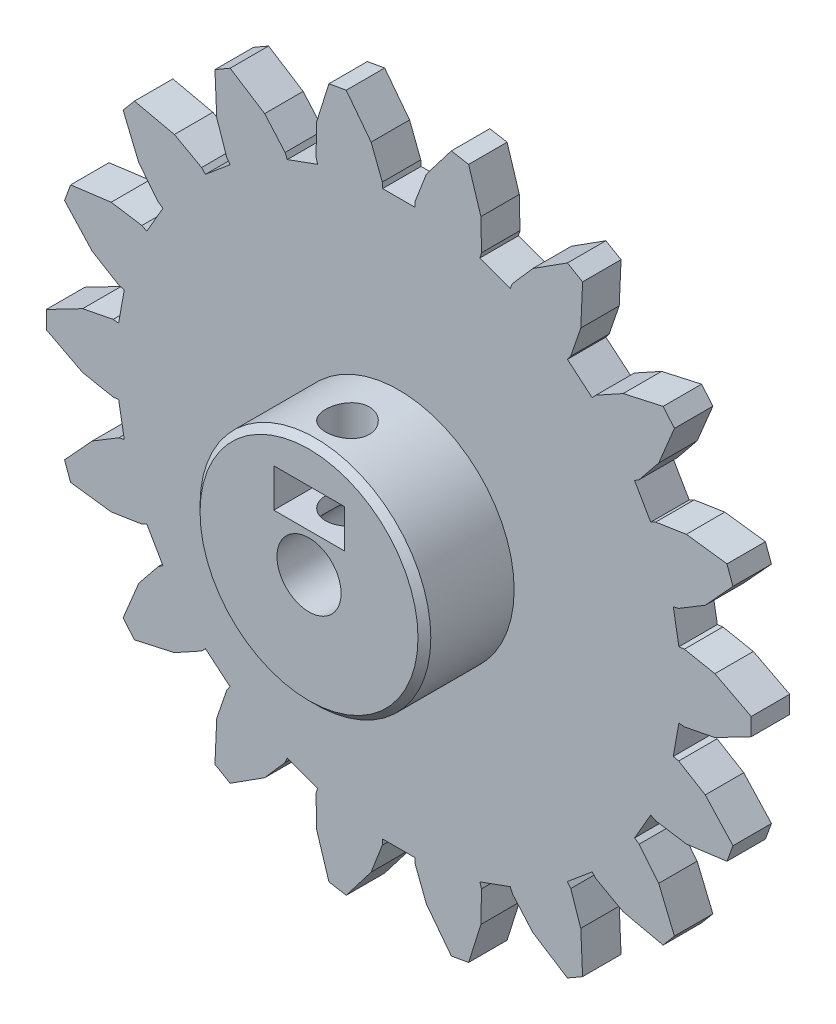
SolidWorks part; units mm, degrees
material "ABS"
ref_plane "Front Plane" through (0, 0, 0) normal (0, 0, 1) x (1, 0, 0)
ref_plane "Top Plane" through (0, 0, 0) normal (0, 1, 0) x (1, 0, 0)
ref_plane "Right Plane" through (0, 0, 0) normal (1, 0, 0) x (0, 0, -1)
sketch "Sketch1" plane through (0, 0, 0) normal (0, 0, 1) x (1, 0, 0)
  line L0 (52.5388, 31.8426) -> (52.9668, 31.8929)
  line L1 (52.9668, 31.8929) -> (55.3456, 31.4261)
  line L2 (55.3456, 31.4261) -> (58.181, 29.9538)
  line L3 (58.181, 29.9538) -> (58.181, 28.5845)
  line L4 (58.181, 28.5845) -> (55.3456, 27.1121)
  line L5 (55.3456, 27.1121) -> (52.9668, 26.6454)
  line L6 (52.9668, 26.6454) -> (52.5388, 26.6957)
  line L7 (52.5388, 26.6957) -> (52.1012, 24.2147)
  line L8 (52.1012, 24.2147) -> (52.5208, 24.1156)
  line L9 (52.5208, 24.1156) -> (54.5964, 22.8636)
  line L10 (54.5964, 22.8636) -> (56.7575, 20.51)
  line L11 (56.7575, 20.51) -> (56.2891, 19.2232)
  line L12 (56.2891, 19.2232) -> (53.1208, 18.8096)
  line L13 (53.1208, 18.8096) -> (50.726, 19.1845)
  line L14 (50.726, 19.1845) -> (50.3409, 19.3783)
  line L15 (50.3409, 19.3783) -> (49.0813, 17.1964)
  line L16 (49.0813, 17.1964) -> (49.4416, 16.9599)
  line L17 (49.4416, 16.9599) -> (50.9638, 15.0733)
  line L18 (50.9638, 15.0733) -> (52.1897, 12.1228)
  line L19 (52.1897, 12.1228) -> (51.3094, 11.0736)
  line L20 (51.3094, 11.0736) -> (48.1906, 11.7686)
  line L21 (48.1906, 11.7686) -> (46.0686, 12.9399)
  line L22 (46.0686, 12.9399) -> (45.7729, 13.2537)
  line L23 (45.7729, 13.2537) -> (43.8429, 11.6343)
  line L24 (43.8429, 11.6343) -> (44.1008, 11.2887)
  line L25 (44.1008, 11.2887) -> (44.8859, 8.9954)
  line L26 (44.8859, 8.9954) -> (45.0287, 5.8036)
  line L27 (45.0287, 5.8036) -> (43.8427, 5.1188)
  line L28 (43.8427, 5.1188) -> (41.1496, 6.8384)
  line L29 (41.1496, 6.8384) -> (39.5561, 8.665)
  line L30 (39.5561, 8.665) -> (39.3857, 9.0611)
  line L31 (39.3857, 9.0611) -> (37.0183, 8.1993)
  line L32 (37.0183, 8.1993) -> (37.1423, 7.7863)
  line L33 (37.1423, 7.7863) -> (37.0957, 5.3628)
  line L34 (37.0957, 5.3628) -> (36.1382, 2.3147)
  line L35 (36.1382, 2.3147) -> (34.7894, 2.0769)
  line L36 (34.7894, 2.0769) -> (32.8471, 4.6136)
  line L37 (32.8471, 4.6136) -> (31.9745, 6.8751)
  line L38 (31.9745, 6.8751) -> (31.9497, 7.3056)
  line L39 (31.9497, 7.3056) -> (29.4305, 7.3056)
  line L40 (29.4305, 7.3056) -> (29.4057, 6.8751)
  line L41 (29.4057, 6.8751) -> (28.5331, 4.6136)
  line L42 (28.5331, 4.6136) -> (26.5908, 2.0769)
  line L43 (26.5908, 2.0769) -> (25.242, 2.3147)
  line L44 (25.242, 2.3147) -> (24.2845, 5.3628)
  line L45 (24.2845, 5.3628) -> (24.2379, 7.7863)
  line L46 (24.2379, 7.7863) -> (24.3618, 8.1993)
  line L47 (24.3618, 8.1993) -> (21.9945, 9.0611)
  line L48 (21.9945, 9.0611) -> (21.8241, 8.665)
  line L49 (21.8241, 8.665) -> (20.2306, 6.8384)
  line L50 (20.2306, 6.8384) -> (17.5375, 5.1188)
  line L51 (17.5375, 5.1188) -> (16.3515, 5.8036)
  line L52 (16.3515, 5.8036) -> (16.4943, 8.9954)
  line L53 (16.4943, 8.9954) -> (17.2794, 11.2887)
  line L54 (17.2794, 11.2887) -> (17.5373, 11.6343)
  line L55 (17.5373, 11.6343) -> (15.6073, 13.2537)
  line L56 (15.6073, 13.2537) -> (15.3116, 12.9399)
  line L57 (15.3116, 12.9399) -> (13.1896, 11.7686)
  line L58 (13.1896, 11.7686) -> (10.0708, 11.0736)
  line L59 (10.0708, 11.0736) -> (9.1905, 12.1228)
  line L60 (9.1905, 12.1228) -> (10.4164, 15.0733)
  line L61 (10.4164, 15.0733) -> (11.9386, 16.9599)
  line L62 (11.9386, 16.9599) -> (12.2989, 17.1964)
  line L63 (12.2989, 17.1964) -> (11.0393, 19.3783)
  line L64 (11.0393, 19.3783) -> (10.6542, 19.1845)
  line L65 (10.6542, 19.1845) -> (8.2594, 18.8096)
  line L66 (8.2594, 18.8096) -> (5.0911, 19.2232)
  line L67 (5.0911, 19.2232) -> (4.6227, 20.51)
  line L68 (4.6227, 20.51) -> (6.7838, 22.8636)
  line L69 (6.7838, 22.8636) -> (8.8594, 24.1156)
  line L70 (8.8594, 24.1156) -> (9.279, 24.2147)
  line L71 (9.279, 24.2147) -> (8.8414, 26.6957)
  line L72 (8.8414, 26.6957) -> (8.4134, 26.6454)
  line L73 (8.4134, 26.6454) -> (6.0345, 27.1121)
  line L74 (6.0345, 27.1121) -> (3.1991, 28.5845)
  line L75 (3.1991, 28.5845) -> (3.1991, 29.9538)
  line L76 (3.1991, 29.9538) -> (6.0345, 31.4261)
  line L77 (6.0345, 31.4261) -> (8.4134, 31.8929)
  line L78 (8.4134, 31.8929) -> (8.8414, 31.8426)
  line L79 (8.8414, 31.8426) -> (9.279, 34.3235)
  line L80 (9.279, 34.3235) -> (8.8594, 34.4227)
  line L81 (8.8594, 34.4227) -> (6.7838, 35.6747)
  line L82 (6.7838, 35.6747) -> (4.6227, 38.0283)
  line L83 (4.6227, 38.0283) -> (5.0911, 39.3151)
  line L84 (5.0911, 39.3151) -> (8.2594, 39.7287)
  line L85 (8.2594, 39.7287) -> (10.6542, 39.3537)
  line L86 (10.6542, 39.3537) -> (11.0393, 39.16)
  line L87 (11.0393, 39.16) -> (12.2989, 41.3418)
  line L88 (12.2989, 41.3418) -> (11.9386, 41.5783)
  line L89 (11.9386, 41.5783) -> (10.4164, 43.4649)
  line L90 (10.4164, 43.4649) -> (9.1905, 46.4155)
  line L91 (9.1905, 46.4155) -> (10.0708, 47.4647)
  line L92 (10.0708, 47.4647) -> (13.1896, 46.7697)
  line L93 (13.1896, 46.7697) -> (15.3116, 45.5984)
  line L94 (15.3116, 45.5984) -> (15.6073, 45.2846)
  line L95 (15.6073, 45.2846) -> (17.5373, 46.904)
  line L96 (17.5373, 46.904) -> (17.2794, 47.2496)
  line L97 (17.2794, 47.2496) -> (16.4943, 49.5429)
  line L98 (16.4943, 49.5429) -> (16.3515, 52.7346)
  line L99 (16.3515, 52.7346) -> (17.5375, 53.4195)
  line L100 (17.5375, 53.4195) -> (20.2306, 51.6999)
  line L101 (20.2306, 51.6999) -> (21.8241, 49.8733)
  line L102 (21.8241, 49.8733) -> (21.9945, 49.4772)
  line L103 (21.9945, 49.4772) -> (24.3618, 50.339)
  line L104 (24.3618, 50.339) -> (24.2379, 50.7519)
  line L105 (24.2379, 50.7519) -> (24.2845, 53.1754)
  line L106 (24.2845, 53.1754) -> (25.242, 56.2236)
  line L107 (25.242, 56.2236) -> (26.5908, 56.4614)
  line L108 (26.5908, 56.4614) -> (28.5331, 53.9247)
  line L109 (28.5331, 53.9247) -> (29.4057, 51.6631)
  line L110 (29.4057, 51.6631) -> (29.4305, 51.2327)
  line L111 (29.4305, 51.2327) -> (31.9497, 51.2327)
  line L112 (31.9497, 51.2327) -> (31.9745, 51.6631)
  line L113 (31.9745, 51.6631) -> (32.8471, 53.9247)
  line L114 (32.8471, 53.9247) -> (34.7894, 56.4614)
  line L115 (34.7894, 56.4614) -> (36.1382, 56.2236)
  line L116 (36.1382, 56.2236) -> (37.0957, 53.1754)
  line L117 (37.0957, 53.1754) -> (37.1423, 50.7519)
  line L118 (37.1423, 50.7519) -> (37.0183, 50.339)
  line L119 (37.0183, 50.339) -> (39.3857, 49.4772)
  line L120 (39.3857, 49.4772) -> (39.5561, 49.8733)
  line L121 (39.5561, 49.8733) -> (41.1496, 51.6999)
  line L122 (41.1496, 51.6999) -> (43.8427, 53.4195)
  line L123 (43.8427, 53.4195) -> (45.0287, 52.7346)
  line L124 (45.0287, 52.7346) -> (44.8859, 49.5429)
  line L125 (44.8859, 49.5429) -> (44.1008, 47.2496)
  line L126 (44.1008, 47.2496) -> (43.8429, 46.904)
  line L127 (43.8429, 46.904) -> (45.7729, 45.2846)
  line L128 (45.7729, 45.2846) -> (46.0686, 45.5984)
  line L129 (46.0686, 45.5984) -> (48.1906, 46.7697)
  line L130 (48.1906, 46.7697) -> (51.3094, 47.4647)
  line L131 (51.3094, 47.4647) -> (52.1897, 46.4155)
  line L132 (52.1897, 46.4155) -> (50.9638, 43.4649)
  line L133 (50.9638, 43.4649) -> (49.4416, 41.5783)
  line L134 (49.4416, 41.5783) -> (49.0813, 41.3418)
  line L135 (49.0813, 41.3418) -> (50.3409, 39.16)
  line L136 (50.3409, 39.16) -> (50.726, 39.3537)
  line L137 (50.726, 39.3537) -> (53.1208, 39.7287)
  line L138 (53.1208, 39.7287) -> (56.2891, 39.3151)
  line L139 (56.2891, 39.3151) -> (56.7575, 38.0283)
  line L140 (56.7575, 38.0283) -> (54.5964, 35.6747)
  line L141 (54.5964, 35.6747) -> (52.5208, 34.4227)
  line L142 (52.5208, 34.4227) -> (52.1012, 34.3235)
  line L143 (52.1012, 34.3235) -> (52.5388, 31.8426)
  line L144 (30.6901, 51.2327) -> (30.6901, 7.3056) construction
  line L145 (58.181, 29.2691) -> (3.1991, 29.2691) construction
sketch "Sketch2" plane through (0, 0, 0) normal (0, 0, 1) x (1, 0, 0)
  line L0 (30.6901, 51.2327) -> (30.6901, 7.3056) construction
  line L1 (58.181, 29.2691) -> (3.1991, 29.2691) construction
  circle A0 centre (30.6901, 29.2691) radius 9
  point P0 (30.6901, 29.2691)
  dimension "D1" = 18
sketch "Sketch3" plane through (0, 0, 0) normal (0, 0, 1) x (1, 0, 0)
  circle A0 centre (30.6901, 29.2691) radius 2.5
  dimension "D1" = 5
extrude "Boss-Extrude1" add sketch "Sketch1" along normal blind 3
extrude "Boss-Extrude2" add sketch "Sketch2" along normal offset from surface (10 mm away) 7 up to face at (30.6901, 29.2691, 3) offset beyond the face yes
extrude "Cut-Extrude1" cut sketch "Sketch3" along normal through all
ref_axis "Axis1" through (30.6901, 29.2691, 10) along (0, 0, -1)
ref_plane "Plane1" through (0, 29.2691, 0) normal (0, 1, 0) x (1, 0, 0)
sketch "Sketch4" plane through (0, 29.2691, 0) normal (0, 1, 0) x (1, 0, 0)
  line L0 (30.6901, -10) -> (30.6901, 0) construction
  line L1 (21.6901, -10) -> (39.6901, -10) construction
  circle A0 centre (30.6901, -7) radius 1.7
  dimension "D1" = 3.4
  dimension "D2" = 3
extrude "Cut-Extrude2" cut sketch "Sketch4" along normal through all
sketch "Sketch6" plane through (0, 0, 10) normal (0, 0, 1) x (1, 0, 0)
  line L0 (30.6901, 38.2691) -> (30.6901, 20.2691) construction
  line L2 (27.9401, 35.2691) -> (33.4401, 35.2691)
  line L3 (27.9401, 35.2691) -> (27.9401, 32.2691)
  line L4 (27.9401, 32.2691) -> (33.4401, 32.2691)
  line L5 (33.4401, 35.2691) -> (33.4401, 32.2691)
  line L6 (27.9401, 35.2691) -> (33.4401, 32.2691) construction
  line L7 (27.9401, 32.2691) -> (33.4401, 35.2691) construction
  circle A0 centre (30.6901, 29.2691) radius 9 construction
  circle A1 centre (30.6901, 29.2691) radius 9 construction
  point P7 (30.6901, 33.7691)
  point P12 (30.6901, 29.2691)
  dimension "D1" = 5.5
  dimension "D2" = 3
  dimension "D3" = 4.5
extrude "Cut-Extrude3" cut sketch "Sketch6" against normal blind 6
chamfer "Chamfer1" distance 0.5 angle 45 1 edges at (21.6901, 29.2691, 10)
ref_axis "Axis2" through (30.6901, 29.2691, 10) along (0, 0, -1)
